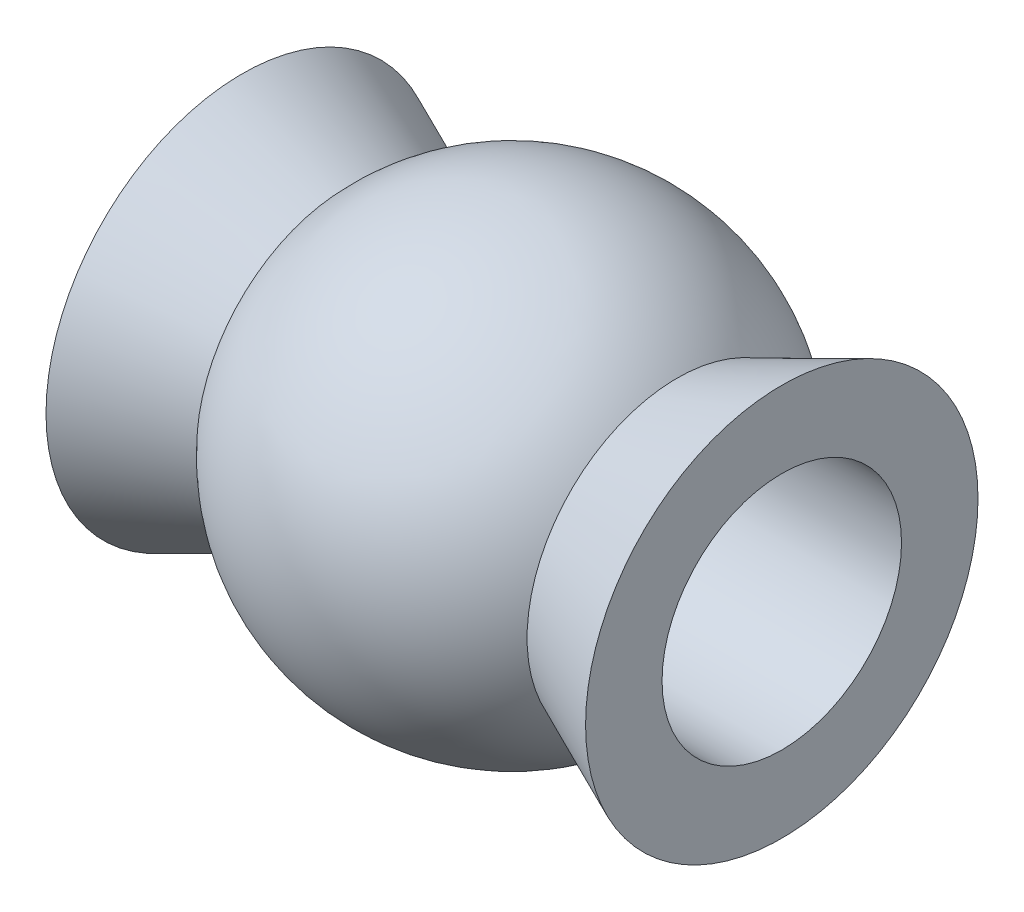
SolidWorks part; units mm, degrees
material "Chrome Stainless Steel"
ref_plane "Front Plane" through (0, 0, 0) normal (0, 0, 1) x (1, 0, 0)
ref_plane "Top Plane" through (0, 0, 0) normal (0, 1, 0) x (1, 0, 0)
ref_plane "Right Plane" through (0, 0, 0) normal (1, 0, 0) x (0, 0, -1)
sketch "Sketch1" plane through (0, 0, 0) normal (0, 1, 0) x (1, 0, 0)
  line L0 (-3.4925, 0) -> (3.4925, 0) construction
  line L1 (3.4925, 0) -> (3.4925, 2.54)
  line L2 (3.4925, 2.54) -> (2.1383, 1.9431)
  line L3 (-2.1383, 1.9431) -> (-3.4925, 2.54)
  line L4 (-3.4925, 2.54) -> (-3.4925, 0)
  line L5 (-3.4925, 0) -> (3.4925, 0)
  arc A0 (2.1383, 1.9431) -> (-2.1383, 1.9431) centre (0, 0) ccw
  dimension "D3" = 2.8892
  dimension "D1" = 6.985
  dimension "D2" = 66.214
  dimension "D4" = 0.9156
  dimension "D5" = 23.786
revolve "Revolve1" add sketch "Sketch1" angle 360 about L0
sketch "Sketch2" plane through (-3.4925, 0, 0) normal (-1, 0, 0) x (0, 0, 1)
  circle A0 centre (0, 0) radius 1.55
extrude "Cut-Extrude1" cut sketch "Sketch2" against normal blind 10
